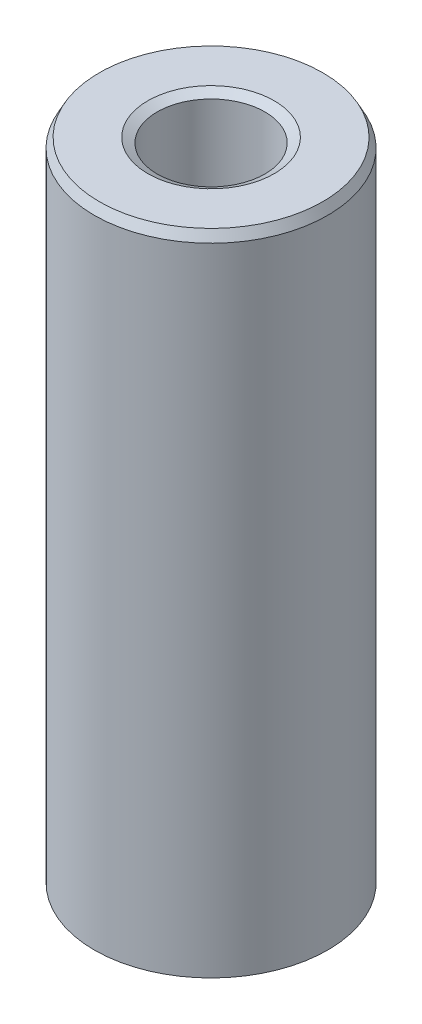
SolidWorks part; units mm, degrees
ref_plane "Front Plane" through (0, 0, 0) normal (0, 0, 1) x (1, 0, 0)
ref_plane "Top Plane" through (0, 0, 0) normal (0, 1, 0) x (1, 0, 0)
ref_plane "Right Plane" through (0, 0, 0) normal (1, 0, 0) x (0, 0, -1)
sketch "Sketch1" plane through (0, 0, 0) normal (0, 1, 0) x (1, 0, 0)
  circle A0 centre (0, 0) radius 25
  dimension "SLEEVE_OD" = 50
extrude "Boss-Extrude1" add sketch "Sketch1" along normal blind 139.3731
sketch "Sketch2" plane through (0, 0, 0) normal (0, 1, 0) x (1, 0, 0)
  circle A0 centre (0, 0) radius 11.5401
  dimension "BORE_D" = 23.0802
extrude "Cut-Extrude1" cut sketch "Sketch2" along normal through all
chamfer "Chamfer1" distance 2.0018 angle 28.001 4 edges at (0, 139.3731, 11.5401) (0, 0, 11.5401) (0, 0, 25) (0, 139.3731, 25) first distance on face at (0, 139.3731, 11.5401) first distance on face at (0, 0, 11.5401) first distance on face at (0, 139.3731, 25)
